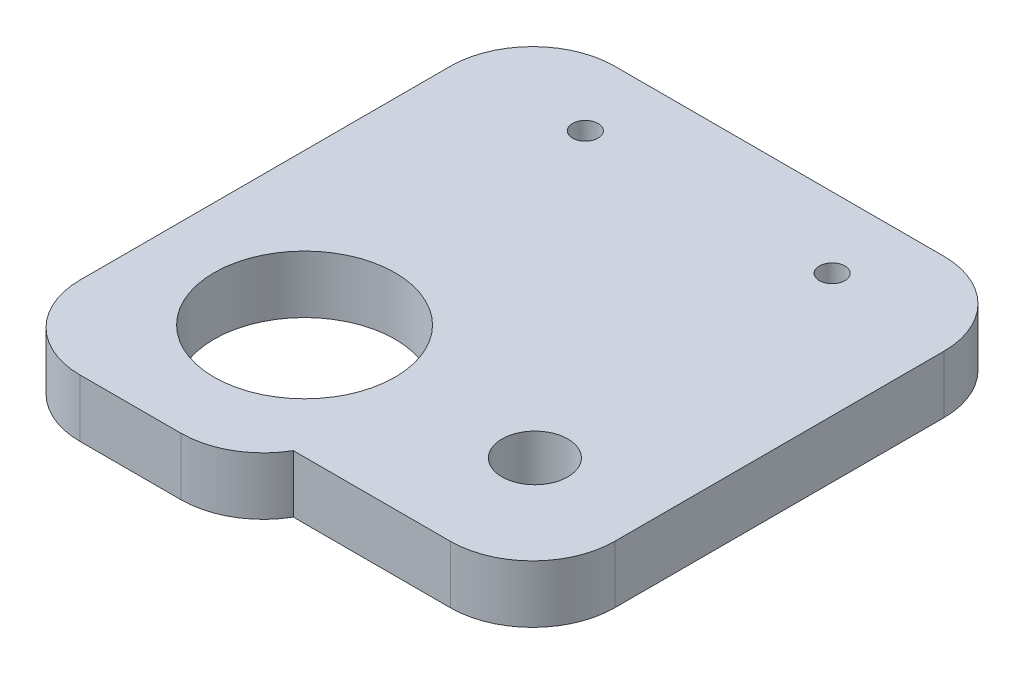
SolidWorks part; units mm, degrees
ref_plane "前视基准面" through (0, 0, 0) normal (0, 0, 1) x (1, 0, 0)
ref_plane "上视基准面" through (0, 0, 0) normal (0, 1, 0) x (1, 0, 0)
ref_plane "右视基准面" through (0, 0, 0) normal (1, 0, 0) x (0, 0, -1)
sketch "草图1" plane through (0, 0, 0) normal (0, 1, 0) x (1, 0, 0)
  line L1 (-25.5, 6.5625) -> (34.5, 6.5625)
  line L2 (-25.5, 6.5625) -> (-25.5, -53.4375)
  line L3 (-25.5, -53.4375) -> (34.5, -53.4375)
  line L4 (34.5, 6.5625) -> (34.5, -53.4375)
  line L5 (-25.5, 6.5625) -> (34.5, -53.4375) construction
  line L6 (-25.5, -53.4375) -> (34.5, 6.5625) construction
  point P4 (4.5, -23.4375)
  dimension "D1" = 60
  dimension "D2" = 60
extrude "凸台-拉伸1" add sketch "草图1" along normal blind 7
sketch "草图2" plane through (0, 0, 0) normal (0, -1, 0) x (1, 0, 0)
  circle A0 centre (20.8714, 39.5245) radius 4
  circle A1 centre (-7.1286, 39.5245) radius 11
  dimension "D1" = 22
  dimension "D2" = 8
extrude "切除-拉伸1" cut sketch "草图2" against normal through all
sketch "草图3" plane through (0, 0, 0) normal (0, -1, 0) x (1, 0, 0)
  line L3 (-25.5, -6.5625) -> (-25.5, 53.4375) construction
  line L4 (34.5, 53.4375) -> (34.5, -6.5625) construction
  circle A0 centre (-10.5, 2.0245) radius 1.55
  circle A1 centre (19.5, 2.0245) radius 1.55
  dimension "D1" = 3.1
  dimension "D2" = 3.1
  dimension "D3" = 15
  dimension "D4" = 15
extrude "切除-拉伸2" cut sketch "草图3" against normal through all
fillet "圆角2" radius 10 3 edges at (34.5, 3.5, 53.4375) (34.5, 3.5, -6.5625) (-25.5, 3.5, -6.5625)
sketch "草图4" plane through (0, 0, 53.4375) normal (0, 0, 1) x (1, 0, 0)
  line L0 (5.4184, 0) -> (5.4184, 7)
  line L1 (-25.5, 0) -> (24.5, 0) construction
  line L2 (-25.5, 7) -> (24.5, 7) construction
  line L3 (5.4184, 7) -> (-25.5, 7)
  line L4 (-25.5, 7) -> (-25.5, 0)
  line L5 (-25.5, 0) -> (5.4184, 0)
extrude "凸台-拉伸2" add sketch "草图4" along normal blind 5
fillet "圆角3" radius 10 2 edges at (5.4184, 3.5, 58.4375) (-25.5, 3.5, 58.4375)
